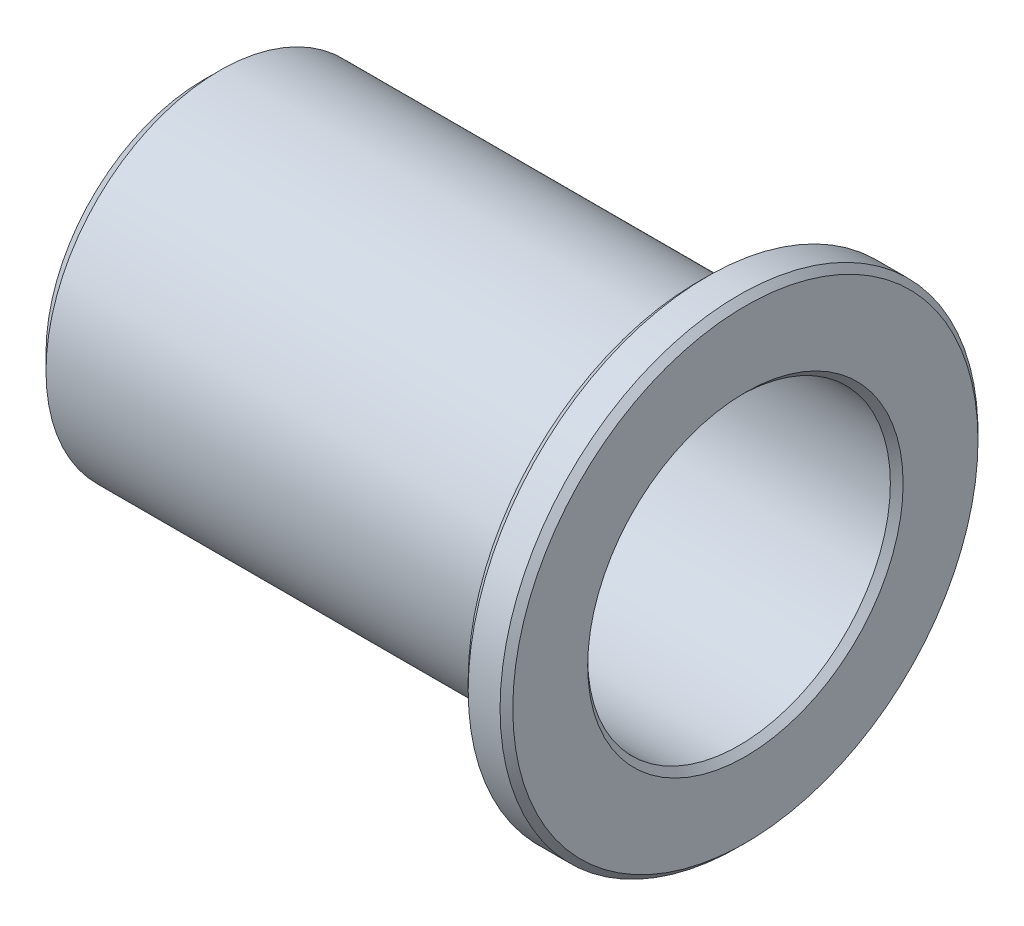
SolidWorks part; units mm, degrees
ref_plane "Спереди" through (0, 0, 0) normal (0, 0, 1) x (1, 0, 0)
ref_plane "Сверху" through (0, 0, 0) normal (0, 1, 0) x (1, 0, 0)
ref_plane "Справа" through (0, 0, 0) normal (1, 0, 0) x (0, 0, -1)
sketch "Эскиз1" plane through (0, 0, 0) normal (0, 0, 1) x (1, 0, 0)
  line L0 (-38.4825, 0) -> (53.8184, 0) construction
  line L18 (-31.1486, 4.75) -> (-31.1486, 4.95)
  line L19 (-14.1486, 4.95) -> (-14.1486, 7.3)
  line L20 (-30.6486, 5.45) -> (-15.6486, 5.45)
  line L21 (-15.6486, 5.45) -> (-15.6486, 7.2)
  line L22 (-15.3486, 7.5) -> (-14.3486, 7.5)
  line L23 (-31.1486, 4.75) -> (-14.3486, 4.75)
  line L24 (-31.1486, 4.95) -> (-30.6486, 5.45)
  line L25 (-15.6486, 7.2) -> (-15.3486, 7.5)
  line L26 (-14.1486, 7.3) -> (-14.3486, 7.5)
  line L27 (-14.3486, 4.75) -> (-14.1486, 4.95)
  point P4 (-31.1486, 5.45)
  point P7 (-14.1486, 7.5)
  point P9 (0, 0)
  point P11 (-15.6486, 7.5)
  point P12 (-14.1486, 4.75)
  point P15 (0, 0)
  point P18 (0, 0)
  point P21 (0, 0)
  dimension "D1" = 17
  dimension "D2" = 15
  dimension "D3" = 10.9
  dimension "D4" = 9.5
  dimension "D5" = 1.5
revolve "Повернуть2" add sketch "Эскиз1" angle 360 about L0
